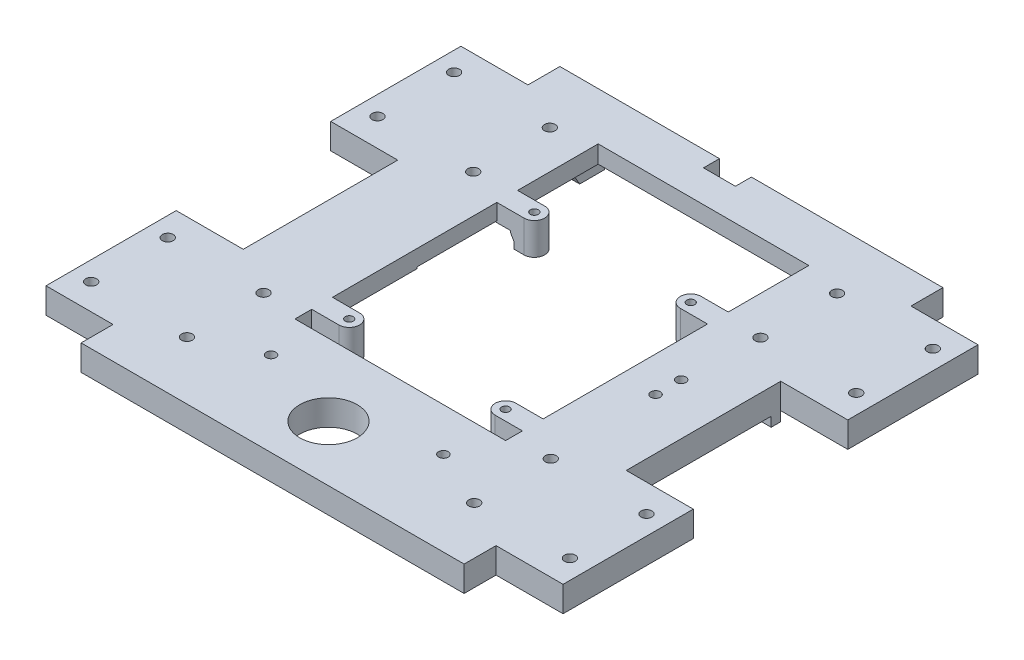
SolidWorks part; units mm, degrees
ref_plane "前视基准面" through (0, 0, 0) normal (0, 0, 1) x (1, 0, 0)
ref_plane "上视基准面" through (0, 0, 0) normal (0, 1, 0) x (1, 0, 0)
ref_plane "右视基准面" through (0, 0, 0) normal (1, 0, 0) x (0, 0, -1)
other "Configuration Table"
sketch "草图1" plane through (0, 0, 0) normal (0, 1, 0) x (1, 0, 0)
  line L1 (-60, 75) -> (60, 75)
  line L2 (-60, 75) -> (-60, -75)
  line L3 (-60, -75) -> (60, -75)
  line L4 (60, 75) -> (60, -75)
  line L5 (-60, 75) -> (60, -75) construction
  line L6 (-60, -75) -> (60, 75) construction
  point P0 (0, 0)
  dimension "D1" = 150
  dimension "D2" = 120
extrude "凸台-拉伸1" add sketch "草图1" along normal blind 8
sketch "草图3" plane through (0, 0, 0) normal (0, -1, 0) x (1, 0, 0)
  line L0 (-60, -75) -> (-60, -24.2) construction
  line L1 (-60, -75) -> (-60, 75) construction
  line L2 (-60, 0) -> (60, 0) construction
  line L3 (60, 75) -> (60, -75) construction
  line L4 (60, 24.2) -> (60, 21.2)
  line L5 (-60, -24.2) -> (60, -24.2)
  line L6 (-60, -24.2) -> (-60, -21.2)
  line L7 (-60, -21.2) -> (60, -21.2)
  line L8 (60, -24.2) -> (60, -21.2)
  line L9 (-60, 21.2) -> (60, 21.2)
  line L10 (-60, 24.2) -> (-60, 21.2)
  line L11 (-60, 24.2) -> (60, 24.2)
  dimension "D1" = 50.8
  dimension "D2" = 3
extrude "凸台-拉伸2" add sketch "草图3" along normal blind 3
sketch "草图5" plane through (0, 8, 0) normal (0, 1, 0) x (1, 0, 0)
  line L0 (0, 75) -> (0, 55) construction
  line L3 (60, 75) -> (-60, 75) construction
  line L4 (28, 55) -> (-28, 55) construction
  line L5 (-28, 55) -> (-28, -30) construction
  line L6 (-28, -30) -> (28, -30) construction
  line L7 (0, -30) -> (0, 55) construction
  line L8 (28, 55) -> (28, -30) construction
  line L9 (33, 60) -> (33, -35)
  line L10 (-33, -35) -> (33, -35)
  line L11 (-33, 60) -> (-33, -35)
  line L12 (33, 60) -> (-33, 60)
  dimension "D1" = 20
  dimension "D2" = 28
  dimension "D3" = 85
  dimension "D4" = 5
extrude "切除-拉伸1" cut sketch "草图5" against normal through all
sketch "草图6" plane through (0, 0, 0) normal (0, -1, 0) x (1, 0, 0)
  line L0 (-60, -24.2) -> (-39, -24.2) construction
  line L1 (-60, -24.2) -> (-33, -24.2) construction
  line L2 (-39, -24.2) -> (-39, -65)
  line L3 (-39, -65) -> (-36, -65)
  line L4 (-36, -65) -> (-36, -24.2)
  line L5 (-36, -24.2) -> (-39, -24.2)
  line L6 (-60, 0) -> (60, 0) construction
  line L7 (-60, -21.2) -> (-60, 21.2) construction
  line L8 (60, 21.2) -> (60, -21.2) construction
  line L9 (0, 75) -> (0, -75) construction
  line L10 (-60, 75) -> (60, 75) construction
  line L11 (60, -75) -> (-60, -75) construction
  line L12 (36, -24.2) -> (39, -24.2)
  line L13 (36, -65) -> (36, -24.2)
  line L14 (39, -65) -> (36, -65)
  line L15 (39, -24.2) -> (39, -65)
  line L16 (39, 24.2) -> (39, 65)
  line L17 (39, 65) -> (36, 65)
  line L18 (36, 65) -> (36, 24.2)
  line L19 (36, 24.2) -> (39, 24.2)
  line L20 (-36, 24.2) -> (-39, 24.2)
  line L21 (-36, 65) -> (-36, 24.2)
  line L22 (-39, 65) -> (-36, 65)
  line L23 (-39, 24.2) -> (-39, 65)
  dimension "D1" = 21
  dimension "D2" = 3
extrude "凸台-拉伸3" add sketch "草图6" along normal blind 3
sketch "草图7" plane through (0, 8, 0) normal (0, 1, 0) x (1, 0, 0)
  line L0 (-81, 65) -> (-60, 65)
  line L1 (-81, 65) -> (-39, 65) construction
  line L2 (-81, 65) -> (-81, 24.2)
  line L3 (-81, 24.2) -> (-60, 24.2)
  line L4 (-39, 24.2) -> (-81, 24.2) construction
  line L5 (-60, 24.2) -> (-60, 65)
  line L6 (0, -6.05) -> (0, 6.05) construction
  line L7 (60, 24.2) -> (60, 65)
  line L8 (81, 24.2) -> (60, 24.2)
  line L9 (81, 65) -> (81, 24.2)
  line L10 (81, 65) -> (60, 65)
  line L11 (-6.05, 0) -> (6.05, 0) construction
  line L12 (81, -65) -> (60, -65)
  line L13 (81, -65) -> (81, -24.2)
  line L14 (81, -24.2) -> (60, -24.2)
  line L15 (60, -24.2) -> (60, -65)
  line L16 (-60, -24.2) -> (-60, -65)
  line L17 (-81, -24.2) -> (-60, -24.2)
  line L18 (-81, -65) -> (-81, -24.2)
  line L19 (-81, -65) -> (-60, -65)
extrude "凸台-拉伸4" add sketch "草图7" against normal blind 8
sketch "草图8" plane through (0, 0, 0) normal (0, -1, 0) x (1, 0, 0)
  line L0 (0, -6.05) -> (0, 6.05) construction
  line L1 (6.05, 0) -> (-6.05, 0) construction
  circle A0 centre (-75, -32.85) radius 1.7
  circle A1 centre (-45, -32.85) radius 1.7
  circle A2 centre (-75, -56.85) radius 1.7
  circle A3 centre (-45, -56.85) radius 1.7
  circle A4 centre (45, -56.85) radius 1.7
  circle A5 centre (75, -56.85) radius 1.7
  circle A6 centre (45, -32.85) radius 1.7
  circle A7 centre (75, -32.85) radius 1.7
  circle A8 centre (75, 32.85) radius 1.7
  circle A9 centre (45, 32.85) radius 1.7
  circle A10 centre (75, 56.85) radius 1.7
  circle A11 centre (45, 56.85) radius 1.7
  circle A12 centre (-45, 56.85) radius 1.7
  circle A13 centre (-75, 56.85) radius 1.7
  circle A14 centre (-45, 32.85) radius 1.7
  circle A15 centre (-75, 32.85) radius 1.7
extrude "切除-拉伸2" cut sketch "草图8" against normal blind 8
sketch "草图9" plane through (0, 8, 0) normal (0, 1, 0) x (1, 0, 0)
  line L0 (28, -30) -> (24.5, -30) construction
  line L1 (-28, -30) -> (28, -30) construction
  line L2 (24.5, -30) -> (24.5, -26.5) construction
  line L3 (24.5, -26.5) -> (24.5, 31.5) construction
  line L4 (24.5, 34.75) -> (24.5, 28.25) construction
  line L5 (24.5, 34.75) -> (33, 34.75)
  line L6 (33, 60) -> (33, -35) construction
  line L7 (24.5, 28.25) -> (33, 28.25)
  line L8 (24.5, -23.25) -> (24.5, -30) construction
  line L9 (24.5, -23.25) -> (33, -23.25)
  line L10 (24.5, -29.75) -> (33, -29.75)
  line L11 (33, -29.75) -> (33, -23.25)
  line L12 (33, 34.75) -> (33, 28.25)
  line L13 (0, -6.05) -> (0, 6.05) construction
  line L14 (-24.5, -23.25) -> (-33, -23.25)
  line L15 (-33, -29.75) -> (-33, -23.25)
  line L16 (-24.5, -29.75) -> (-33, -29.75)
  line L17 (-24.5, 34.75) -> (-33, 34.75)
  line L18 (-24.5, 28.25) -> (-33, 28.25)
  line L19 (-33, 34.75) -> (-33, 28.25)
  circle A1 centre (24.5, 31.5) radius 1.25
  circle A2 centre (24.5, -26.5) radius 1.25
  arc A3 (24.5, 34.75) -> (24.5, 28.25) centre (24.5, 31.5) ccw
  circle A4 centre (24.5, 31.5) radius 3.25 construction
  arc A5 (24.5, -23.25) -> (24.5, -29.75) centre (24.5, -26.5) ccw
  circle A6 centre (24.5, -26.5) radius 3.25 construction
  circle A7 centre (-24.5, -26.5) radius 1.25
  arc A8 (-24.5, -23.25) -> (-24.5, -29.75) centre (-24.5, -26.5) cw
  circle A9 centre (-24.5, 31.5) radius 1.25
  arc A10 (-24.5, 34.75) -> (-24.5, 28.25) centre (-24.5, 31.5) cw
  dimension "D4" = 2.5
  dimension "D5" = 2.5
  dimension "D6" = 2
  dimension "D8" = 2.5
  dimension "D1" = 3.5
  dimension "D2" = 3.5
  dimension "D3" = 58
  dimension "D7" = 2
extrude "凸台-拉伸5" add sketch "草图9" against normal blind 8
sketch "草图10" plane through (0, 8, 0) normal (0, 1, 0) x (1, 0, 0)
  line L0 (33, 60) -> (33, -35) construction
  line L1 (-33, 60) -> (33, 60)
  line L2 (-33, 60) -> (-33, 40)
  line L3 (-33, 40) -> (33, 40)
  line L4 (33, 60) -> (33, 40)
  dimension "D1" = 66
  dimension "D2" = 20
extrude "凸台-拉伸6" add sketch "草图10" against normal blind 2
sketch "草图11" plane through (0, -3, 0) normal (0, -1, 0) x (1, 0, 0)
  line L0 (-39, -24.2) -> (-54, -24.2)
  line L1 (-60, -24.2) -> (-39, -24.2) construction
  line L2 (-54, -24.2) -> (-54, -21.2)
  line L3 (-33, -21.2) -> (-60, -21.2) construction
  line L4 (-54, -21.2) -> (-33, -21.2)
  line L5 (-33, -21.2) -> (-33, -24.2)
  line L6 (-33, -24.2) -> (-36, -24.2)
  line L7 (-36, -24.2) -> (-36, -54.2)
  line L8 (-36, -65) -> (-36, -24.2) construction
  line L9 (-36, -54.2) -> (-39, -54.2)
  line L10 (-39, -24.2) -> (-39, -65) construction
  line L11 (-39, -54.2) -> (-39, -24.2)
  line L12 (6.05, 0) -> (-6.05, 0) construction
  line L13 (-36, 54.2) -> (-39, 54.2)
  line L14 (-36, 24.2) -> (-36, 54.2)
  line L15 (-33, 24.2) -> (-36, 24.2)
  line L16 (-33, 21.2) -> (-33, 24.2)
  line L17 (-54, 21.2) -> (-33, 21.2)
  line L18 (-54, 24.2) -> (-54, 21.2)
  line L19 (-39, 24.2) -> (-54, 24.2)
  line L20 (-39, 54.2) -> (-39, 24.2)
  line L21 (0, -6.05) -> (0, 6.05) construction
  line L22 (36, 24.2) -> (36, 54.2)
  line L23 (33, 24.2) -> (36, 24.2)
  line L24 (33, 21.2) -> (33, 24.2)
  line L25 (54, 21.2) -> (33, 21.2)
  line L26 (54, 24.2) -> (54, 21.2)
  line L27 (39, 24.2) -> (54, 24.2)
  line L28 (39, 54.2) -> (39, 24.2)
  line L29 (36, 54.2) -> (39, 54.2)
  line L30 (36, -54.2) -> (39, -54.2)
  line L31 (36, -24.2) -> (36, -54.2)
  line L32 (33, -24.2) -> (36, -24.2)
  line L33 (33, -21.2) -> (33, -24.2)
  line L34 (54, -21.2) -> (33, -21.2)
  line L35 (54, -24.2) -> (54, -21.2)
  line L36 (39, -24.2) -> (54, -24.2)
  line L37 (39, -54.2) -> (39, -24.2)
  dimension "D1" = 15
  dimension "D2" = 30
extrude "切除-拉伸3" cut sketch "草图11" against normal blind 3
sketch "草图12" plane through (0, 6, 0) normal (0, -1, 0) x (1, 0, 0)
  line L4 (-33, -40) -> (-33, -60)
  line L5 (-33, -60) -> (33, -60)
  line L6 (33, -60) -> (33, -40)
  line L7 (33, -40) -> (-33, -40)
  line L8 (-33, -40) -> (-33, -60)
  line L9 (-33, -60) -> (33, -60)
  line L10 (33, -60) -> (33, -40)
  line L11 (33, -40) -> (-33, -40)
  dimension "D1" = 0
extrude "切除-拉伸4" cut sketch "草图12" against normal up to next
sketch "草图13" plane through (0, 0, 0) normal (0, -1, 0) x (1, 0, 0)
  line L0 (-36, -62.5) -> (36, -62.5)
  line L1 (-36, -65) -> (-36, -54.2) construction
  line L2 (36, -54.2) -> (36, -65) construction
  line L3 (33, -60) -> (-33, -60) construction
  line L4 (-36, -62.5) -> (-36, 37.5)
  line L8 (-28.75, 35) -> (-28.75, -60)
  line L9 (-28.75, -60) -> (28.75, -60)
  line L10 (28.75, 35) -> (-28.75, 35)
  line L11 (-33, 35) -> (33, 35) construction
  line L12 (36, 37.5) -> (-36, 37.5)
  line L13 (0, -6.05) -> (0, 6.05) construction
  line L14 (36, -62.5) -> (36, 37.5)
  line L15 (28.75, 35) -> (28.75, -60)
  point P15 (0, 37.5)
  point P20 (0, -60)
  point P22 (0, 35)
  dimension "D1" = 2.5
  dimension "D2" = 2.5
extrude "切除-拉伸5" cut sketch "草图13" against normal blind 2.5
chamfer "倒角1" distance 2 angle 30 4 edges at (28.75, 0, 26.5) (28.75, 0, -31.5) (-28.75, 0, -31.5) (-28.75, 0, 26.5) first distance on face at (28.75, 1.25, 26.5) first distance on face at (28.75, 1.25, -31.5) first distance on face at (-28.75, 1.25, -31.5) first distance on face at (-28.75, 1.25, 26.5)
chamfer "倒角2" distance 3 angle 60 8 edges at (37.5, -3, 54.2) (54, -3, 22.7) (54, -3, -22.7) (37.5, -3, -54.2) (-37.5, -3, -54.2) (-54, -3, -22.7) (-54, -3, 22.7) (-37.5, -3, 54.2) first distance on face at (37.5, -3, 59.6) first distance on face at (57, -3, 22.7) first distance on face at (57, -3, -22.7) first distance on face at (37.5, -3, -59.6) first distance on face at (-37.5, -3, -59.6) first distance on face at (-57, -3, -22.7) first distance on face at (-57, -3, 22.7) first distance on face at (-37.5, -3, 59.6)
sketch "草图14" plane through (0, 0, 0) normal (0, -1, 0) x (1, 0, 0)
  line L0 (-33, -28.25) -> (-33, -3.25)
  line L1 (-33, -28.25) -> (-33, 23.25) construction
  line L2 (-33, -3.25) -> (-47, -3.25)
  line L3 (-47, -3.25) -> (-47, -28.25)
  line L4 (-47, -28.25) -> (-33, -28.25)
  dimension "D1" = 25
  dimension "D2" = 14
extrude "切除-拉伸6" cut sketch "草图14" against normal blind 3
sketch "草图15" plane through (0, 0, 0) normal (0, -1, 0) x (1, 0, 0)
  line L3 (-24.5, -28.25) -> (-27.5953, -28.25)
  line L4 (-27.5953, -28.25) -> (-27.5953, -34.75)
  line L5 (-27.5953, -34.75) -> (-24.5, -34.75)
  line L6 (-24.5, -28.25) -> (-27.5953, -28.25)
  line L7 (-27.5953, -28.25) -> (-27.5953, -34.75)
  line L8 (-27.5953, -34.75) -> (-24.5, -34.75)
  line L9 (-24.5, 29.75) -> (-27.5953, 29.75)
  line L10 (-27.5953, 29.75) -> (-27.5953, 23.25)
  line L11 (-27.5953, 23.25) -> (-24.5, 23.25)
  line L12 (-24.5, 29.75) -> (-27.5953, 29.75)
  line L13 (-27.5953, 29.75) -> (-27.5953, 23.25)
  line L14 (-27.5953, 23.25) -> (-24.5, 23.25)
  line L15 (24.5, 23.25) -> (27.5953, 23.25)
  line L16 (27.5953, 23.25) -> (27.5953, 29.75)
  line L17 (27.5953, 29.75) -> (24.5, 29.75)
  line L18 (24.5, 23.25) -> (27.5953, 23.25)
  line L19 (27.5953, 23.25) -> (27.5953, 29.75)
  line L20 (27.5953, 29.75) -> (24.5, 29.75)
  line L21 (24.5, -34.75) -> (27.5953, -34.75)
  line L22 (27.5953, -34.75) -> (27.5953, -28.25)
  line L23 (27.5953, -28.25) -> (24.5, -28.25)
  line L24 (24.5, -34.75) -> (27.5953, -34.75)
  line L25 (27.5953, -34.75) -> (27.5953, -28.25)
  line L26 (27.5953, -28.25) -> (24.5, -28.25)
  circle A0 centre (-24.5, 26.5) radius 1.25 construction
  arc A1 (-24.5, -34.75) -> (-24.5, -28.25) centre (-24.5, -31.5) ccw
  arc A2 (-24.5, -34.75) -> (-24.5, -28.25) centre (-24.5, -31.5) ccw
  arc A3 (-24.5, 23.25) -> (-24.5, 29.75) centre (-24.5, 26.5) ccw
  arc A4 (-24.5, 23.25) -> (-24.5, 29.75) centre (-24.5, 26.5) ccw
  arc A5 (24.5, 29.75) -> (24.5, 23.25) centre (24.5, 26.5) ccw
  arc A6 (24.5, 29.75) -> (24.5, 23.25) centre (24.5, 26.5) ccw
  arc A7 (24.5, -28.25) -> (24.5, -34.75) centre (24.5, -31.5) ccw
  arc A8 (24.5, -28.25) -> (24.5, -34.75) centre (24.5, -31.5) ccw
  circle A9 centre (-24.5, 26.5) radius 1.25
  circle A10 centre (24.5, 26.5) radius 1.25 construction
  circle A11 centre (24.5, 26.5) radius 1.25
  circle A12 centre (-24.5, -31.5) radius 1.25 construction
  circle A13 centre (-24.5, -31.5) radius 1.25
  circle A14 centre (24.5, -31.5) radius 1.25 construction
  circle A15 centre (24.5, -31.5) radius 1.25
  dimension "D1" = 0
  dimension "D2" = 0
  dimension "D3" = 0
  dimension "D4" = 0
extrude "凸台-拉伸8" add sketch "草图15" along normal blind 2
sketch "草图16" plane through (0, 0, 0) normal (0, -1, 0) x (1, 0, 0)
  line L0 (0, -75) -> (0, -70)
  line L1 (60, -75) -> (-60, -75) construction
  line L2 (0, -70) -> (-10, -70)
  line L3 (-10, -70) -> (-10, -75)
  line L4 (-10, -75) -> (0, -75)
  line L5 (0, 37.5) -> (0, 57.5) construction
  line L6 (36, 37.5) -> (-36, 37.5) construction
  circle A1 centre (0, 57.5) radius 9
  dimension "D4" = 18
  dimension "D1" = 5
  dimension "D2" = 10
  dimension "D3" = 20
extrude "切除-拉伸7" cut sketch "草图16" against normal up to next contours A1 | L4 L0 L2 L3
sketch "草图17" plane through (0, 0, 0) normal (0, -1, 0) x (1, 0, 0)
  line L0 (0, 37.5) -> (0, 48.5) construction
  line L1 (36, 37.5) -> (-36, 37.5) construction
  line L2 (0, 48.5) -> (27, 48.5) construction
  line L3 (0, 48.5) -> (-27, 48.5) construction
  circle A0 centre (0, 57.5) radius 9 construction
  circle A1 centre (-27, 48.5) radius 1.5
  circle A2 centre (27, 48.5) radius 1.5
  dimension "D4" = 3
  dimension "D5" = 3
  dimension "D1" = 27
  dimension "D2" = 27
  dimension "D3" = 11
extrude "切除-拉伸8" cut sketch "草图17" against normal up to next
sketch "草图18" plane through (0, 0, 0) normal (0, -1, 0) x (1, 0, 0)
  line L0 (36, -8.984) -> (44, -8.984) construction
  line L1 (36, -55.4679) -> (36, 37.5) construction
  line L2 (44, -8.984) -> (44, -0.984) construction
  circle A0 centre (44, -0.984) radius 1.5
  circle A1 centre (44, -8.984) radius 1.5
  dimension "D3" = 3
  dimension "D4" = 3
  dimension "D1" = 8
  dimension "D2" = 8
extrude "切除-拉伸9" cut sketch "草图18" against normal up to next
